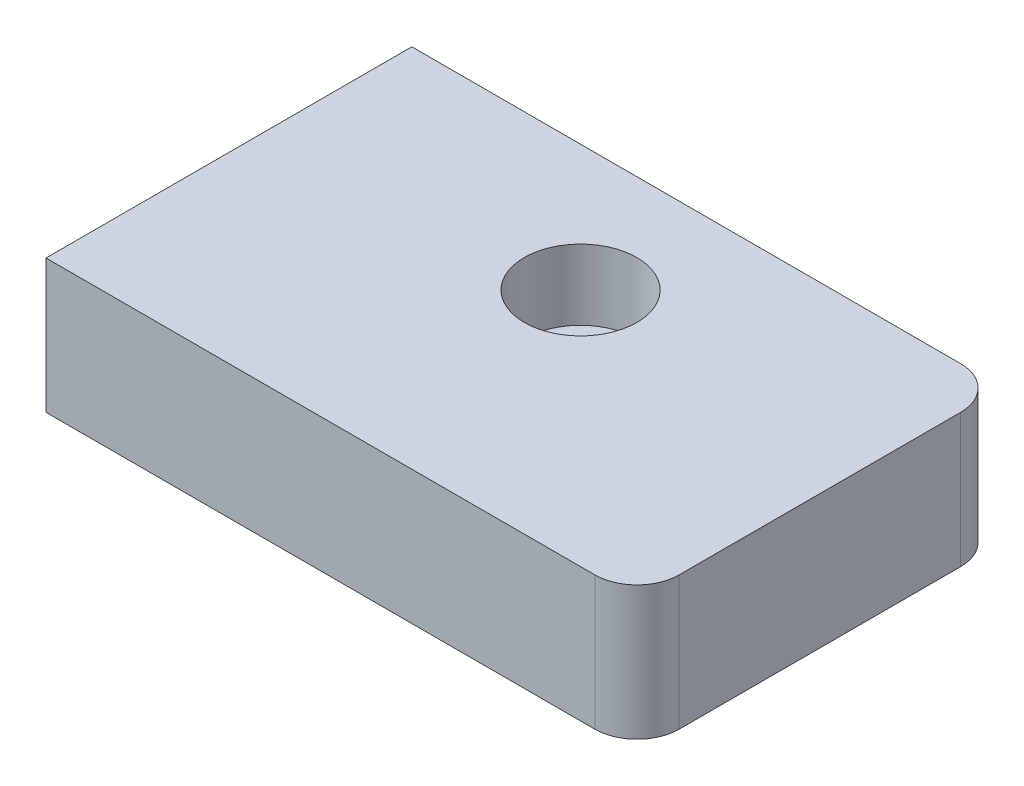
SolidWorks part; units mm, degrees
ref_plane "前视基准面" through (0, 0, 0) normal (0, 0, 1) x (1, 0, 0)
ref_plane "上视基准面" through (0, 0, 0) normal (0, 1, 0) x (1, 0, 0)
ref_plane "右视基准面" through (0, 0, 0) normal (1, 0, 0) x (0, 0, -1)
sketch "草图1" plane through (0, 0, 0) normal (0, 1, 0) x (1, 0, 0)
  line L1 (-21, 13) -> (21, 13)
  line L2 (-21, 13) -> (-21, -13)
  line L3 (-21, -13) -> (21, -13)
  line L4 (21, 13) -> (21, -13)
  line L5 (-21, 13) -> (21, -13) construction
  line L6 (-21, -13) -> (21, 13) construction
  point P0 (0, 0)
  dimension "D1" = 42
  dimension "D2" = 26
extrude "凸台-拉伸1" add sketch "草图1" along normal blind 9.5
sketch "草图2" plane through (0, 9.5, 0) normal (0, 1, 0) x (1, 0, 0)
  circle A0 centre (-0.0356, 4.0262) radius 4
  dimension "D1" = 8
extrude "切除-拉伸1" cut sketch "草图2" against normal blind 5
fillet "圆角1" radius 3 2 edges at (21, 4.75, -13) (21, 4.75, 13)
